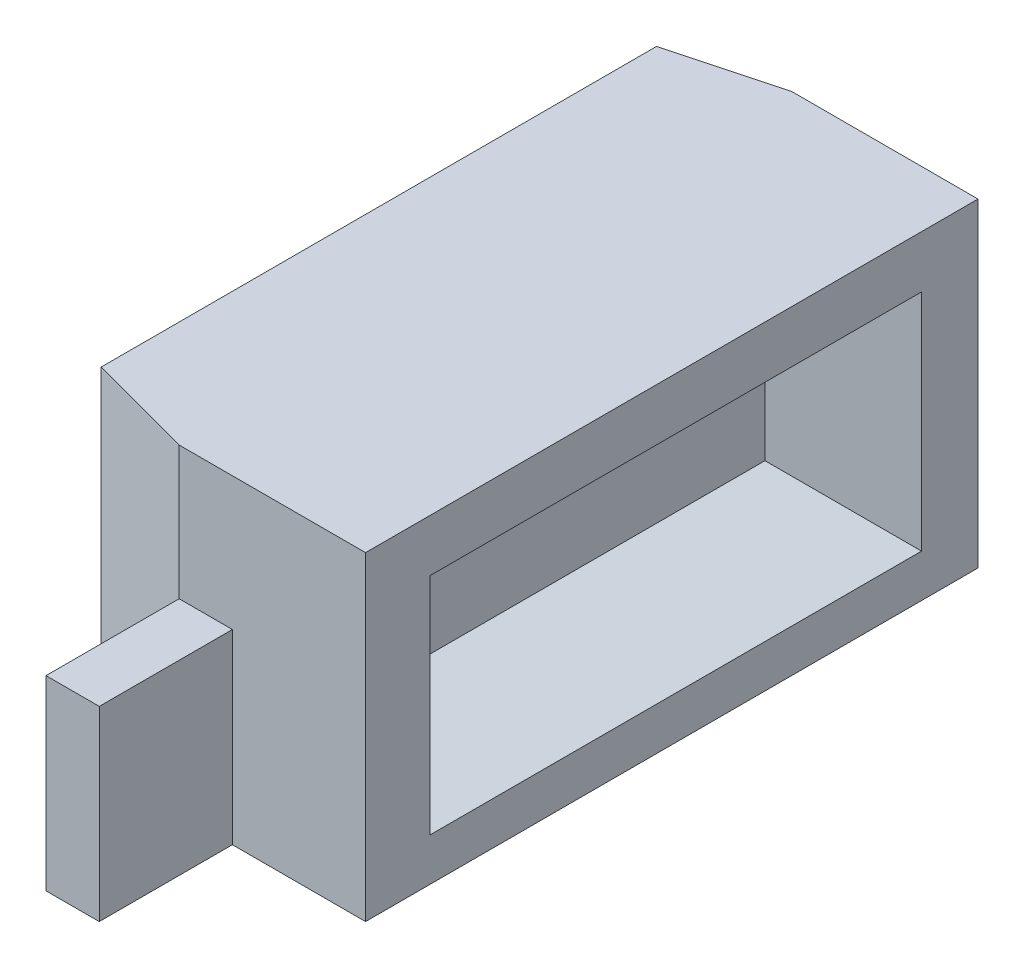
SolidWorks part; units mm, degrees
ref_plane "Front Plane" through (0, 0, 0) normal (0, 0, 1) x (1, 0, 0)
ref_plane "Top Plane" through (0, 0, 0) normal (0, 1, 0) x (1, 0, 0)
ref_plane "Right Plane" through (0, 0, 0) normal (1, 0, 0) x (0, 0, -1)
sketch "Sketch1" plane through (0, 0, 0) normal (0, 1, 0) x (1, 0, 0)
  line L1 (-0.55, -1.15) -> (0.55, -1.15)
  line L2 (-0.55, -1.15) -> (-0.55, 1.15)
  line L3 (-0.55, 1.15) -> (0.55, 1.15)
  line L4 (0.55, -1.15) -> (0.55, 1.15)
  line L5 (-0.55, -1.15) -> (0.55, 1.15) construction
  line L6 (-0.55, 1.15) -> (0.55, -1.15) construction
  point P0 (0, 0)
  dimension "D1" = 2.3
  dimension "D2" = 1.1
extrude "Boss-Extrude1" add sketch "Sketch1" along normal blind 1.2
sketch "Sketch2" plane through (0, 0, 0) normal (0, -1, 0) x (1, 0, 0)
  line L0 (-0.55, 1.15) -> (0.55, 1.15) construction
  line L1 (-0.15, 1.15) -> (0.05, 1.15)
  line L2 (-0.15, 1.15) -> (-0.15, 1.65)
  line L3 (-0.15, 1.65) -> (0.05, 1.65)
  line L4 (0.05, 1.15) -> (0.05, 1.65)
  line L5 (0.55, -1.15) -> (-0.55, -1.15) construction
  line L6 (-0.15, -1.15) -> (0.05, -1.15)
  line L7 (-0.15, -1.15) -> (-0.15, -1.65)
  line L8 (-0.15, -1.65) -> (0.05, -1.65)
  line L9 (0.05, -1.15) -> (0.05, -1.65)
  line L10 (-0.55, -1.15) -> (-0.55, 1.15) construction
  dimension "D1" = 0.2
  dimension "D2" = 0.2
  dimension "D3" = 0.5
  dimension "D4" = 0.5
  dimension "D5" = 0.4
  dimension "D6" = 0.4
extrude "Boss-Extrude2" add sketch "Sketch2" against normal blind 0.7
sketch "Sketch3" plane through (0.55, 0, 0) normal (1, 0, 0) x (0, 0, -1)
  line L1 (-0.9081, 1.0041) -> (0.938, 1.0041)
  line L2 (-0.9081, 1.0041) -> (-0.9081, 0.1609)
  line L3 (-0.9081, 0.1609) -> (0.938, 0.1609)
  line L4 (0.938, 1.0041) -> (0.938, 0.1609)
extrude "Cut-Extrude1" cut sketch "Sketch3" against normal blind 0.5
draft "Draft1" type of draft neutral plane draft angle 10 faces to draft 4 face at (0.3, 0.1609, -0.015) face at (0.3, 0.5825, 0.9081) face at (0.3, 1.0041, -0.015) face at (0.3, 0.5825, -0.938) neutral plane through (0.55, 1.2, 1.15) neutral plane normal (1, 0, 0) parameters "D1"=10
chamfer "Chamfer1" distance 0.4 angle 15 2 edges at (-0.55, 0.6, 1.15) (-0.55, 0.6, -1.15) first distance on face at (-0.0813, 0.5625, 1.15) first distance on face at (0.0312, 0.5625, -1.15)
